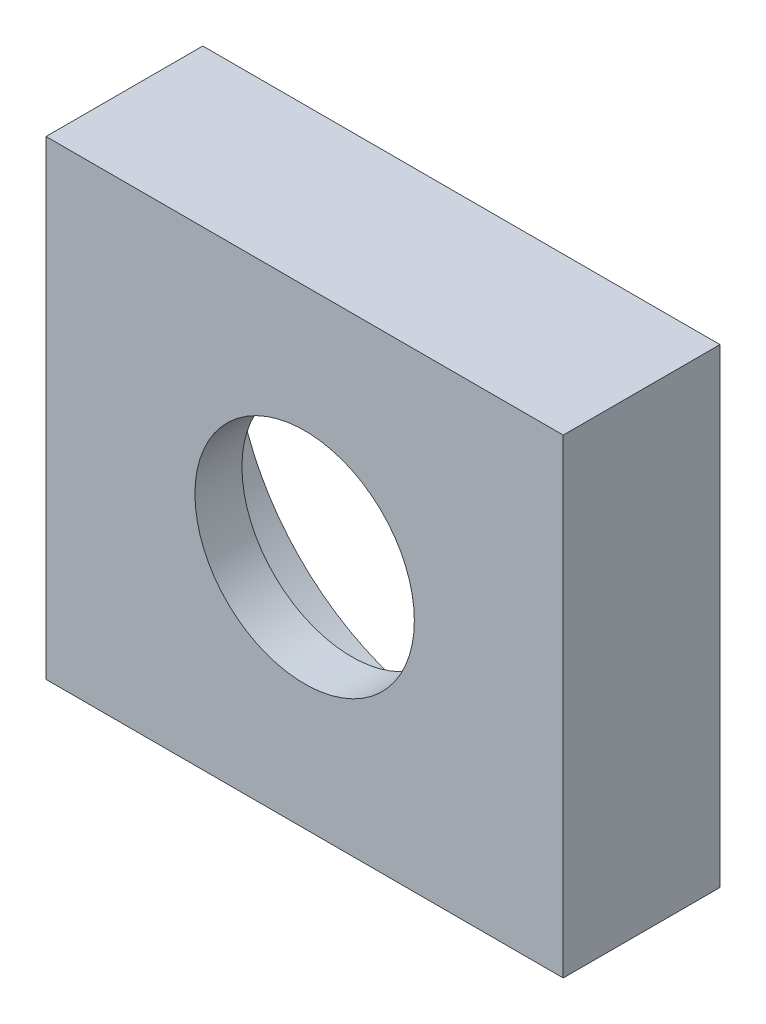
SolidWorks part; units mm, degrees
material "POM Acetal Copolymer"
ref_plane "Front Plane" through (0, 0, 0) normal (0, 0, 1) x (1, 0, 0)
ref_plane "Top Plane" through (0, 0, 0) normal (0, 1, 0) x (1, 0, 0)
ref_plane "Right Plane" through (0, 0, 0) normal (1, 0, 0) x (0, 0, -1)
sketch "Sketch1" plane through (0, 0, 0) normal (0, 0, 1) x (1, 0, 0)
  line L1 (0, 0) -> (33, 0)
  line L2 (0, 0) -> (0, 30)
  line L3 (0, 30) -> (33, 30)
  line L4 (33, 0) -> (33, 30)
  dimension "D1" = 30
  dimension "D2" = 33
extrude "Boss-Extrude1" add sketch "Sketch1" along normal blind 10
sketch "Sketch2" plane through (0, 0, 10) normal (0, 0, 1) x (1, 0, 0)
  line L0 (0, 30) -> (0, 0) construction
  line L1 (0, 0) -> (33, 0) construction
  circle A0 centre (16.5, 15) radius 7
  dimension "D1" = 14
  dimension "D2" = 16.5
  dimension "D3" = 15
extrude "Cut-Extrude1" cut sketch "Sketch2" against normal up to next
sketch "Sketch3" plane through (0, 0, 0) normal (0, 0, -1) x (-1, 0, 0)
  circle A0 centre (-16.5, 15) radius 14.5
  dimension "D1" = 29
extrude "Cut-Extrude2" cut sketch "Sketch3" against normal offset from surface (7 mm away) 3 up to face at (23.5, 15, 10)
hole_wizard "Tap Drill for M3 Tap2" positions "Sketch5" profile "Sketch4" hole size "M3" standard "ISO"
sketch "Sketch5" plane through (0, 0, 0) normal (0, -1, 0) x (-1, 0, 0)
  line L0 (0, -10) -> (-33, -10) construction
  line L1 (-33, -10) -> (-33, 0) construction
  line L2 (0, -10) -> (0, 0) construction
  point P0 (-3, -6)
  point P2 (-30, -6)
  dimension "D1" = 4
  dimension "D2" = 3
  dimension "D3" = 3
sketch "Sketch4" plane through (3, 0, 6) normal (1, 0, 0) x (0, 0, -1)
  line L0 (0, 0) -> (0, 8.7511)
  line L1 (0, 8.7511) -> (1.25, 8)
  line L2 (1.25, 8) -> (1.25, 0)
  line L5 (1.25, 0) -> (0, 0)
  line L10 (0, 8.7511) -> (-1.25, 8) construction
  line L11 (0, -6.35) -> (0, 107.95) construction
  dimension "Hole Dia." = 2.5
  dimension "Hole Depth" = 8
  dimension "Drill Angle" = 118
